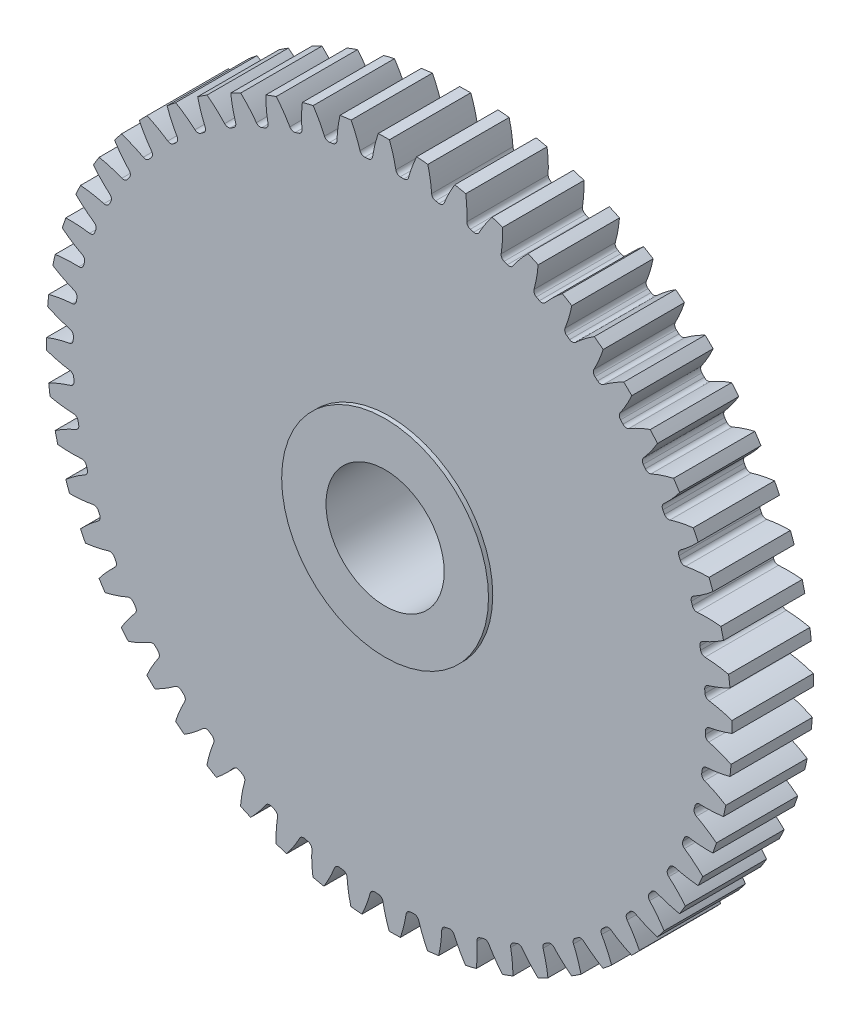
SolidWorks part; units mm, degrees
ref_plane "Front" through (0, 0, 0) normal (0, 0, 1) x (1, 0, 0)
ref_plane "Top" through (0, 0, 0) normal (0, 1, 0) x (1, 0, 0)
ref_plane "Right" through (0, 0, 0) normal (1, 0, 0) x (0, 0, -1)
sketch "Sketch3" plane through (0, 0, 0) normal (0, 0, 1) x (1, 0, 0)
  circle A0 centre (0, 0) radius 36.83
  dimension "od" = 73.66
extrude "gearBody" add sketch "Sketch3" along normal blind 8.7376
sketch "Sketch2" plane through (0, 0, 0) normal (0, 0, 1) x (1, 0, 0)
  line L0 (0, 0) -> (31.8067, 13.1748) construction
  line L1 (42.9048, -8.6911) -> (0, 0) construction
  line L2 (0, 0) -> (36.3143, 0) construction
  line L3 (35.5574, -0.4275) -> (35.4773, -2.4239) construction
  line L5 (35.5174, -1.4257) -> (0, 0) construction
  line L7 (0, 0) -> (34.4273, 0) construction
  arc A0 (34.4204, -0.6909) -> (34.365, -2.0702) centre (0, 0) ccw construction
  arc A1 (36.83, -0.0107) -> (36.7124, -2.9414) centre (0, 0) ccw construction
  arc A2 (35.5574, -0.4275) -> (35.4773, -2.4239) centre (0, 0) ccw construction
  arc A3 (33.9497, -1.5528) -> (33.9649, -1.1733) centre (0, 0) ccw
  arc A4 (42.9048, -8.6911) -> (34.3185, -2.0575) centre (30.6484, -15.6818) ccw
  arc A5 (42.9048, -8.6911) -> (43.4634, 5.2242) centre (0, 0) ccw
  arc A6 (43.4634, 5.2242) -> (34.373, -0.6998) centre (31.8067, 13.1748) cw
  arc A7 (33.9649, -1.1733) -> (34.373, -0.6998) centre (34.4638, -1.1906) cw
  arc A8 (34.3185, -2.0575) -> (33.9497, -1.5528) centre (34.4483, -1.5756) cw
  point P6 (43.4634, 5.2242)
  point P22 (42.9048, -8.6911)
  dimension "baseDia" = 68.8547
  dimension "od" = 73.66
  dimension "pd" = 71.12
  dimension "rd" = 67.9704
  dimension "rFillet" = 0.4991
  dimension "pointX" = 43.4634
  dimension "pointY" = 5.2242
  dimension "CTT" = 1.9964
  dimension "flankCenterAngle" = 22.5
extrude "toothCut" cut sketch "Sketch2" along normal through all
pattern_circular "CirPattern1" count 56 over 360 about axis through (0, 0, 8.7376) along (0, 0, -1) of "toothCut"
sketch "hub1Dia" plane through (0, 0, 0) normal (0, 0, -1) x (-1, 0, 0)
  circle A0 centre (0, 0) radius 25.4
  dimension "hub1Dia" = 50.8
extrude "hub1" [suppressed] add sketch "hub1Dia" along normal blind 19.05
sketch "hub2Dia" plane through (0, 0, 8.7376) normal (0, 0, 1) x (1, 0, 0)
  circle A0 centre (0, 0) radius 21.844
  dimension "hub2dia" = 43.688
extrude "hub2" [suppressed] add sketch "hub2Dia" along normal blind 16.002
sketch "boreDia" plane through (0, 0, 0) normal (0, 0, 1) x (1, 0, 0)
  circle A0 centre (0, 0) radius 6.35
  dimension "boreDia" = 12.7
extrude "bore" cut sketch "boreDia" against normal mid plane 25400
chamfer "hub2Chamfer" [suppressed] distance 0.508 angle 45
chamfer "hub2BoreChamfer" [suppressed] distance 0.508 angle 45
chamfer "hub1BoreChamfer" [suppressed] distance 0.508 angle 45
chamfer "hub1Chamfer" [suppressed] distance 0.508 angle 45
chamfer "BoreChamfer2" [suppressed] distance 0.508 angle 45
chamfer "boreChamfer1" [suppressed] distance 0.508 angle 45
sketch "Sketch4" plane through (0, 0, 0) normal (0, 0, -1) x (-1, 0, 0)
  circle A0 centre (0, 0) radius 11.1125
  circle A1 centre (0, 0) radius 6.35
  dimension "D1" = 22.225
extrude "Boss-Extrude1" add sketch "Sketch4" along normal blind 0.4572
sketch "Sketch5" plane through (0, 0, 8.7376) normal (0, 0, 1) x (1, 0, 0)
  circle A0 centre (0, 0) radius 6.35
  circle A1 centre (0, 0) radius 11.1125
  dimension "D1" = 22.225
extrude "Boss-Extrude2" add sketch "Sketch5" along normal blind 0.4572
